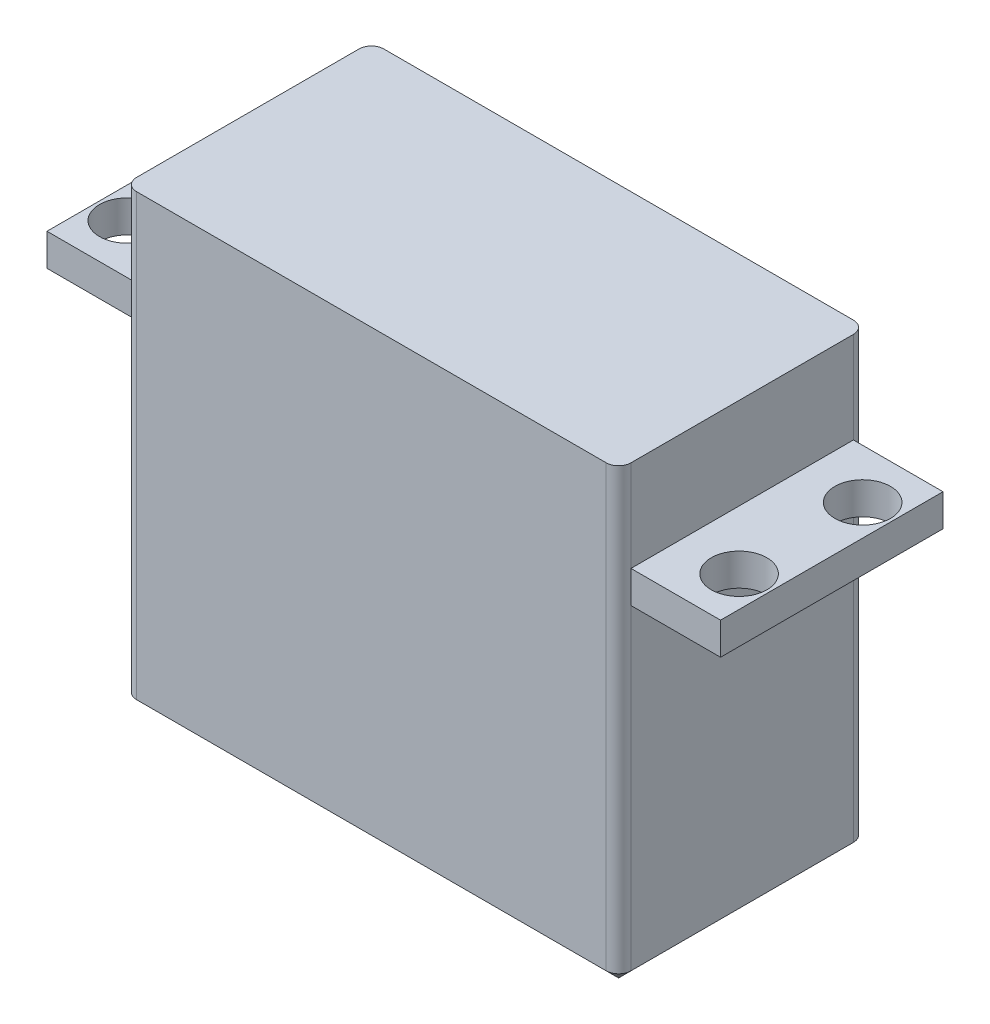
SolidWorks part; units mm, degrees
material "Polyetheretherketone (PEEK)"
ref_plane "Front Plane" through (0, 0, 0) normal (0, 0, 1) x (1, 0, 0)
ref_plane "Top Plane" through (0, 0, 0) normal (0, 1, 0) x (1, 0, 0)
ref_plane "Right Plane" through (0, 0, 0) normal (1, 0, 0) x (0, 0, -1)
sketch "Sketch1" plane through (0, 0, 0) normal (0, 1, 0) x (1, 0, 0)
  line L1 (-20, 10) -> (20, 10)
  line L2 (-20, 10) -> (-20, -10)
  line L3 (-20, -10) -> (20, -10)
  line L4 (20, 10) -> (20, -10)
  line L5 (-20, 10) -> (20, -10) construction
  line L6 (-20, -10) -> (20, 10) construction
  point P0 (0, 0)
  dimension "D1" = 20
  dimension "D2" = 40
extrude "Boss-Extrude1" add sketch "Sketch1" along normal blind 36.6
sketch "Sketch2" plane through (20, 0, 0) normal (1, 0, 0) x (0, 0, -1)
  line L0 (-10, 0) -> (10, 0) construction
  line L1 (-9, 29.2) -> (9, 29.2)
  line L2 (-9, 29.2) -> (-9, 26.6)
  line L3 (-9, 26.6) -> (9, 26.6)
  line L4 (9, 29.2) -> (9, 26.6)
  dimension "D1" = 26.6
  dimension "D2" = 2.6
  dimension "D3" = 18
  dimension "D4" = 9
extrude "Boss-Extrude2" add sketch "Sketch2" along normal blind 7.25
sketch "Sketch3" plane through (0, 29.2, 0) normal (0, 1, 0) x (1, 0, 0)
  circle A0 centre (24.75, 5) radius 2.25
  dimension "D2" = 4.5
  dimension "D1" = 5
  dimension "D3" = 24.75
extrude "Cut-Extrude1" cut sketch "Sketch3" against normal through all
mirror "Mirror2" about plane through (0, 0, 0) normal (0, 0, 1) of "Cut-Extrude1"
mirror "Mirror3" about plane through (0, 0, 0) normal (1, 0, 0) of "Boss-Extrude2", "Cut-Extrude1", "Mirror2"
sketch "Sketch4" plane through (0, 36.6, 0) normal (0, 1, 0) x (1, 0, 0)
  point P5 (9.9, 0)
fillet "Fillet1" radius 1 4 edges at (20, 18.3, 10) (20, 18.3, -10) (-20, 18.3, -10) (-20, 18.3, 10)
chamfer "Chamfer1" distance 1 angle 45 8 edges at (20, 0, 0) (0, 0, 10) (-20, 0, 0) (19.7071, 0, 9.7071) (-19.7071, 0, 9.7071) (19.7071, 0, -9.7071) (-19.7071, 0, -9.7071) (0, 0, -10)
ref_axis "Axis1" through (9.9, 36.6, 0) along (0, 1, 0)
